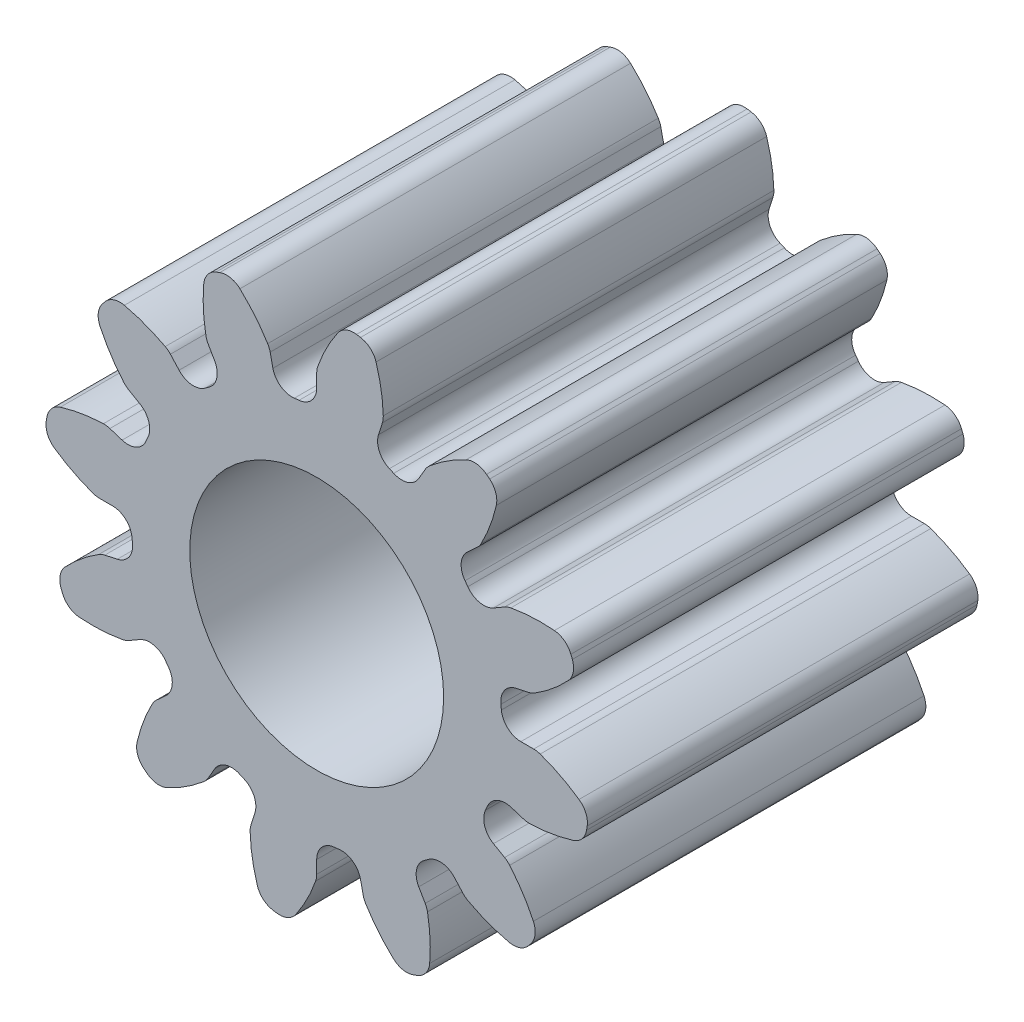
SolidWorks part; units mm, degrees
ref_plane "Front Plane" through (0, 0, 0) normal (1, 0, 0) x (0, 1, 0)
ref_plane "Top Plane" through (0, 0, 0) normal (0, 0, 1) x (0, 1, 0)
ref_plane "Right Plane" through (0, 0, 0) normal (0, 1, 0) x (-1, 0, 0)
sketch "Sketch1" plane through (0, 0, 0) normal (0, 0, 1) x (0, 1, 0)
  line L1 (0, 0) -> (0, 5.6382) construction
  line L2 (0, 0) -> (2.1576, 5.209) construction
  line L3 (0, 0) -> (3.9868, 3.9868) construction
  line L4 (0, 0) -> (5.209, 2.1576) construction
  line L5 (0, 0) -> (5.6382, 0) construction
  line L6 (2.1576, 5.209) -> (0.1121, 6.0563) construction
  line L8 (3.9868, 3.9868) -> (0.8556, 7.118) construction
  line L9 (5.209, 2.1576) -> (2.6671, 8.2943) construction
  line L11 (5.6382, 0) -> (5.6382, 8.8564) construction
  line L12 (0, 0) -> (0.9187, 5.9292) construction
  line L14 (1.7063, 5.3738) -> (0, 0) construction
  line L17 (0, 5.6382) -> (0, 4.75)
  line L18 (1.7063, 5.3738) -> (1.4375, 4.5273)
  line L19 (0.1369, 5.9984) -> (0, 0) construction
  circle A16 centre (0, 0) radius 5.6382 construction
  arc A17 (1.4182, 6.8548) -> (0.7228, 6.9626) centre (0, 0) ccw
  circle A18 centre (0, 0) radius 4.75
  arc A19 (0, 6) -> (1.8158, 5.7186) centre (0, 0) ccw construction
  arc A20 (0, 6) -> (1.8158, 5.7186) centre (0, 0) cw construction
  arc A21 (0, 5.6382) -> (2.6671, 8.2943) centre (3.9437, 4.3453) cw construction
  arc A22 (1.7063, 5.3738) -> (-0.0319, 8.7125) centre (-2.4438, 5.335) ccw construction
  arc A23 (0, 5.6382) -> (0.7228, 6.9626) centre (3.9437, 4.3453) cw
  arc A24 (1.4182, 6.8548) -> (1.7063, 5.3738) centre (-2.4438, 5.335) cw
  circle A25 centre (0, 0) radius 3.25
  point P12 (0, 0)
  dimension "BaseCircle" = 11.2763
  dimension "AddendumCircle" = 14
  dimension "RootCircle" = 9.5
  dimension "PitchCircle" = 12
  dimension "D6" = 6.5
  dimension "D2" = 8.8564
  dimension "D3" = 6.6423
  dimension "D4" = 4.4282
  dimension "D5" = 2.2141
  dimension "D7" = 7.5
  dimension "D1" = 5
extrude "Boss-Extrude5" add sketch "Sketch1" along normal blind 10 contours A18 A19 A20 region at (-4.5612, 0.7068, 0)
extrude "Boss-Extrude8" add sketch "Sketch1<14>" along normal blind 10 contours A24 A17 A23 A16 region at (-5.6937, 0.8822, 0)
sketch "Sketch1<14>" plane through (0, 0, 0) normal (0, 0, 1) x (0, 1, 0) same geometry as "Sketch1"
fillet "Fillet6" radius 0.5 6 edges at (-6.8548, 1.4182, 5) (-6.9626, 0.7228, 5) (-5.6382, 0, 5) (-4.75, 0, 5) (-5.3738, 1.7063, 5) (-4.5273, 1.4375, 5)
pattern_circular "CirPattern1" count 12 over 360 about axis through (0, 0, 10) along (0, 0, -1) of "Boss-Extrude8", "Fillet6"
equation "\"SunTeeth\"= 12"
equation "\"Module\" = 1"
equation "\"PressureAngle\" = 20deg"
equation "\"PitchDiameter\"= \"SunTeeth\" * \"Module\""
equation "\"OutsideDiameter\"= (\"SunTeeth\" + 2) * \"Module\""
equation "\"WholeDepthDia\"= (\"SunTeeth\" - 2.5) * \"Module\""
equation "\"BaseCircleDia\"= \"PitchDiameter\" * cos(\"PressureAngle\")"
equation "\"Addendum\"= 1 * \"Module\""
equation "\"Dedendum\"= 1.25 * \"Module\""
equation "\"WholeDepth\"= 2.25 * \"Module\""
equation "\"CircularPitch\"= 360 / \"SunTeeth\""
equation "\"FilletRadius\"= \"Module\" / 2"
equation "\"PitchArcLength\"= ( \"CircularPitch\" / 180 * 3.14 * \"BaseCircleDia\" / 2 )"
equation "\"BaseCircle@Sketch1\" = \"BaseCircleDia\""
equation "\"AddendumCircle@Sketch1\"= \"PitchCircle@Sketch1\" + \"Addendum\" * 2"
equation "\"RootCircle@Sketch1\"=\"PitchCircle@Sketch1\" - \"Dedendum\" * 2"
equation "\"PitchCircle@Sketch1\" = \"Module\" * \"SunTeeth\""
equation "\"InvoluteArrayMaxLength\"= \"BaseCircleDia\" * pi / 4"
equation "\"D2@Sketch1\"=\"InvoluteArrayMaxLength\""
equation "\"D3@Sketch1\"=\"InvoluteArrayMaxLength\"*3/4"
equation "\"D4@Sketch1\"=\"InvoluteArrayMaxLength\"*2/4"
equation "\"D5@Sketch1\"=\"InvoluteArrayMaxLength\"*1/4"
equation "\"GearWidth\"=10"
equation "\"ShaftDiameter\"= 6.5"
equation "\"D6@Sketch1\" = IIF ( \"PitchCircle@Sketch1\" > \"ShaftDiameter\" , \"ShaftDiameter\" , \"PitchCircle@Sketch1\" - 3 )"
equation "\"D1\"= \"SunTeeth\""
equation "\"D1\"= \"GearWidth\""
equation "\"D7@Sketch1\"=\"CircularPitch\"/4"
equation "\"D1@CirPattern1\"=\"SunTeeth\""
